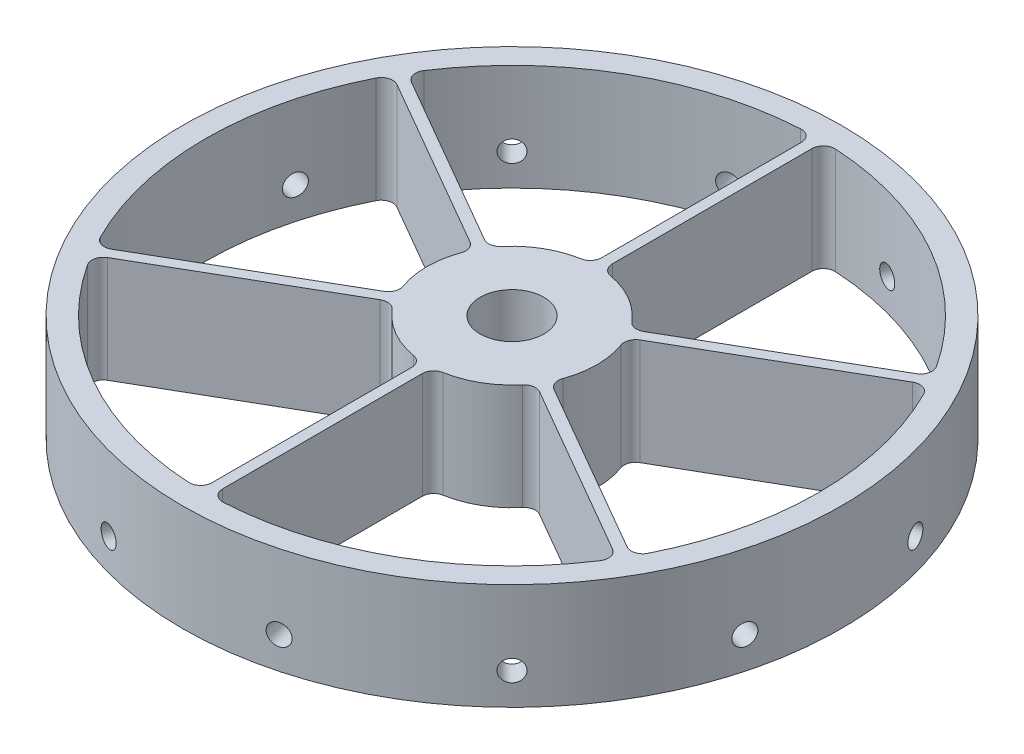
SolidWorks part; units mm, degrees
material "6061-T6 (SS)"
ref_plane "Front Plane" through (0, 0, 0) normal (0, 0, 1) x (1, 0, 0)
ref_plane "Top Plane" through (0, 0, 0) normal (0, 1, 0) x (1, 0, 0)
ref_plane "Right Plane" through (0, 0, 0) normal (1, 0, 0) x (0, 0, -1)
sketch "ring" plane through (0, 0, 0) normal (0, 1, 0) x (1, 0, 0)
  line L0 (0, 25.4) -> (0, 91.567) construction
  line L1 (25.4, 0) -> (91.567, 0) construction
  line L2 (0, -25.4) -> (0, -91.567) construction
  line L3 (-25.4, 0) -> (-91.567, 0) construction
  line L4 (-1.5883, 25.3503) -> (-1.5883, 91.5532)
  line L5 (1.5867, 25.3504) -> (1.5867, 91.5533)
  circle A0 centre (0, 0) radius 25.4
  circle A1 centre (0, 0) radius 91.567
  circle A2 centre (0, 0) radius 98.425
  dimension "D1" = 50.8
  dimension "D3" = 196.85
  dimension "D2" = 6.858
  dimension "D4" = 1.5867
  dimension "D5" = 3.175
sketch "beam" plane through (0, 0, 0) normal (0, 1, 0) x (1, 0, 0)
  line L1 (1.5875, 25.3503) -> (1.5875, 97.7771)
  line L3 (-1.5875, 25.3503) -> (-1.5875, 97.7771)
  line L4 (0, 25.4) -> (0, 91.567) construction
  circle A2 centre (0, 0) radius 25.4 construction
  circle A4 centre (0, 0) radius 97.79 construction
  arc A5 (1.5875, 25.3503) -> (-1.5875, 25.3503) centre (0, 0) ccw
  arc A6 (1.5875, 97.7771) -> (-1.5875, 97.7771) centre (0, 0) ccw
  dimension "D3" = 50.8
  dimension "D4" = 195.58
  dimension "D1" = 1.5875
  dimension "D2" = 3.175
extrude "Boss-Extrude1" add sketch "ring" along normal mid plane 31.75 contours A2 A1 | A0 A1 region at (0, 0, 0) region at (-95.6411, 0, 0)
ref_axis "Axis1" through (0, 21.8355, 0) along (0, -1, 0)
extrude "Boss-Extrude2" add sketch "beam" along normal mid plane 31.75 contours L1 A6 L3 A5
ref_plane "Plane1" through (0, 0, 0) normal (-0.2588, 0, -0.9659) x (0, -1, 0)
pattern_circular "CirPattern1" count 6 over 360 about axis through (0, 21.8355, 0) along (0, -1, 0) of "Boss-Extrude2"
sketch "Sketch3" plane through (0, 0, 0) normal (0, 1, 0) x (1, 0, 0)
  circle A0 centre (0, 0) radius 9.525
  dimension "D1" = 19.05
split line "Split Line1"
sketch "Sketch4" plane through (0, 0, 0) normal (0, 1, 0) x (1, 0, 0)
  line L0 (-21.1603, 14.05) -> (-78.4937, 47.1514) construction
  line L1 (104.5183, -60.3437) -> (119.2332, -68.8393)
  line L2 (-21.1603, 14.05) -> (-78.4937, 47.1514) construction
split line "Split Line2" [suppressed]
fillet "Fillet1" radius 3.429 24 edges at (-80.0812, 0, 44.4018) (-80.0812, 0, -44.4018) (-22.7478, 0, 11.3004) (-22.7478, 0, -11.3004) (-21.1603, 0, -14.05) (-1.5875, 0, -25.3503) (-78.4937, 0, -47.1514) (-1.5875, 0, -91.5532) (1.5875, 0, -91.5532) (78.4937, 0, -47.1514) (21.1603, 0, -14.05) (1.5875, 0, -25.3503) (22.7478, 0, 11.3004) (22.7478, 0, -11.3004) (80.0812, 0, 44.4018) (80.0812, 0, -44.4018) (1.5875, 0, 91.5532) (1.5875, 0, 25.3503) (21.1603, 0, 14.05) (78.4937, 0, 47.1514) (-1.5875, 0, 91.5532) (-1.5875, 0, 25.3503) (-21.1603, 0, 14.05) (-78.4937, 0, 47.1514)
sketch "Sketch8" plane through (0, 15.875, 0) normal (0, 1, 0) x (1, 0, 0)
  circle A0 centre (0, 0) radius 9.525
  circle A1 centre (0, 0) radius 9.525 construction
extrude "Cut-Extrude1" cut sketch "Sketch8" against normal through all
sketch "Sketch10" plane through (0, 0, 0) normal (-0.2588, 0, -0.9659) x (0, -1, 0)
  line L1 (15.875, -9.525) -> (15.875, 9.525) construction
  circle A1 centre (19.05, 0) radius 3.175
  circle A2 centre (6.35, 0) radius 3.175
  dimension "D1" = 6.35
  dimension "D2" = 6.35
  dimension "D3" = 12.7
  dimension "D4" = 9.525
extrude "Cut-Extrude2" cut sketch "Sketch10" along normal through all from offset 38.1
pattern_circular "CirPattern3" count 12 over 360 about axis through (0, 15.875, 0) along (0, -1, 0) of "Cut-Extrude2" reverse direction yes
equation "\"H\"= 1.25"
equation "\"D1@Boss-Extrude2\"=\"H\""
equation "\"D\"= 2"
equation "\"a\"= .125"
equation "\"T\"= .27"
equation "\"N\"= 6"
equation "\"D1@CirPattern1\"=\"N\""
equation "\"D1@Boss-Extrude1\"=\"H\""
equation "\"D2@beam\"=\"a\""
equation "\"D1@beam\"=\"a\"/2"
equation "\"D2@ring\"=\"T\""
equation "\"D1@ring\"=\"D\""
equation "\"rodD\"= 0.75"
equation "\"D1@Sketch3\"=\"rodD\""
